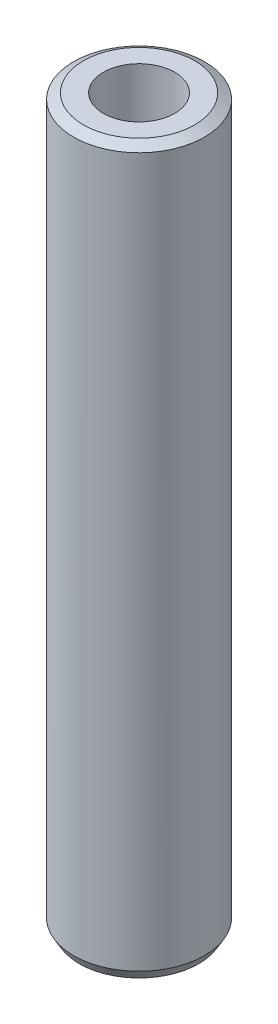
SolidWorks part; units mm, degrees
ref_plane "Front Plane" through (0, 0, 0) normal (0, 0, 1) x (1, 0, 0)
ref_plane "Top Plane" through (0, 0, 0) normal (0, 1, 0) x (1, 0, 0)
ref_plane "Right Plane" through (0, 0, 0) normal (1, 0, 0) x (0, 0, -1)
sketch "Sketch1" plane through (0, 0, 0) normal (0, 1, 0) x (1, 0, 0)
  circle A0 centre (0, 0) radius 42.5
  dimension "SHAFT_OD" = 85
extrude "Boss-Extrude1" add sketch "Sketch1" along normal blind 470.4752
sketch "Sketch2" plane through (0, 0, 0) normal (0, 1, 0) x (1, 0, 0)
  circle A0 centre (0, 0) radius 23.1758
  dimension "BORE_D" = 46.3517
extrude "Cut-Extrude1" cut sketch "Sketch2" along normal through all
chamfer "Chamfer1" distance 3.6871 angle 60 2 edges at (0, 470.4752, 42.5) (0, 0, 42.5) first distance on face at (0, 470.4752, 42.5) first distance on face at (0, 0, 23.1758)
